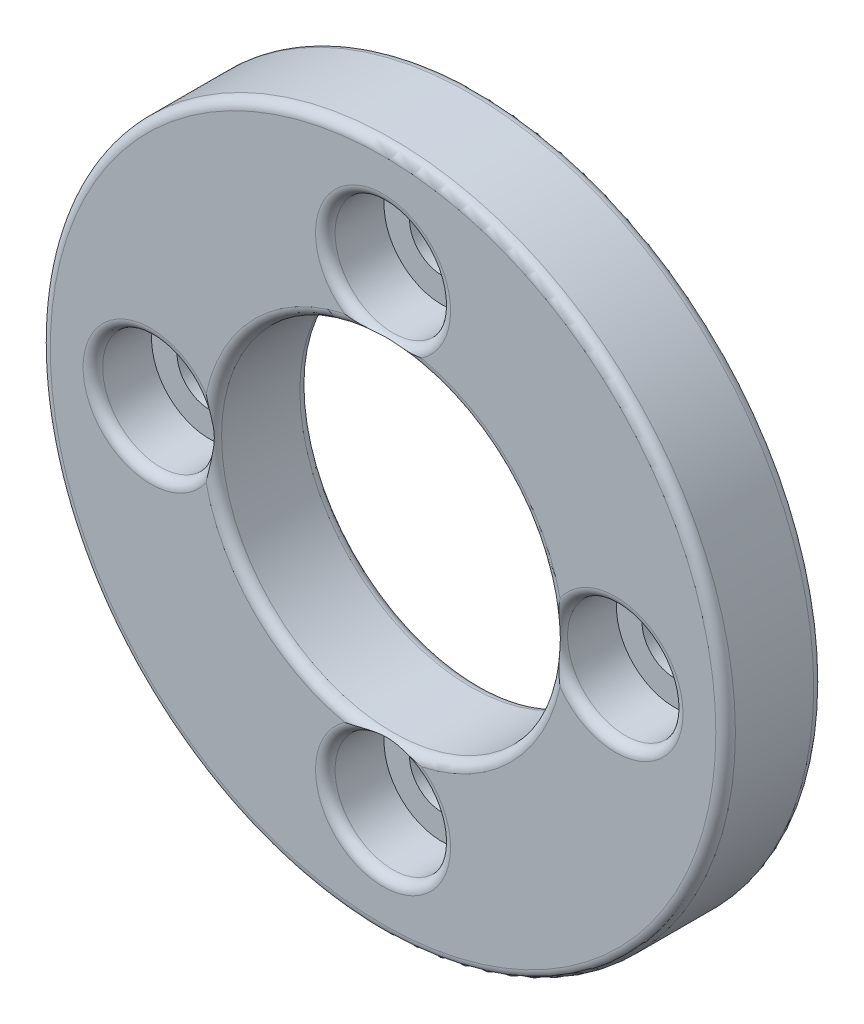
SolidWorks part; units mm, degrees
ref_plane "Ebene vorne" through (0, 0, 0) normal (0, 0, 1) x (1, 0, 0)
ref_plane "Ebene oben" through (0, 0, 0) normal (0, 1, 0) x (1, 0, 0)
ref_plane "Ebene rechts" through (0, 0, 0) normal (1, 0, 0) x (0, 0, -1)
sketch "Skizze1" plane through (0, 0, 0) normal (0, 0, 1) x (1, 0, 0)
  line L0 (0, 8.75) -> (0, 10.225) construction
  line L1 (0, 13.525) -> (0, 15) construction
  circle A0 centre (0, 0) radius 15
  circle A1 centre (0, 0) radius 8.75
  circle A2 centre (0, 0) radius 17.5
  circle A3 centre (0, 11.875) radius 1.65
  circle A4 centre (11.875, 0) radius 1.65
  circle A5 centre (0, -11.875) radius 1.65
  circle A6 centre (-11.875, 0) radius 1.65
  point P18 (0, 0)
  dimension "D1" = 30
  dimension "D2" = 17.5
  dimension "D3" = 35
  dimension "D4" = 3.3
  dimension "D5" = 4
extrude "Aufsatz-Linear austragen1" add sketch "Skizze1" along normal blind 5 contours A0 A6 A5 A4 A3 A1 | A2 A0 region at (-14.5757, 0, 0) region at (-17.005, 0, 0)
sketch "Skizze2" plane through (0, 0, 5) normal (0, 0, 1) x (1, 0, 0)
  circle A0 centre (0, 11.875) radius 2.95
  circle A1 centre (11.875, 0) radius 2.95
  circle A2 centre (0, -11.875) radius 2.95
  circle A3 centre (-11.875, 0) radius 2.95
  point P12 (0, 0)
  dimension "D1" = 5.9
  dimension "D2" = 4
extrude "Schnitt-Linear austragen1" cut sketch "Skizze2" against normal blind 3
fillet "Verrundung1" radius 0.5 12 edges at (17.5, 0, 0) (8.75, 0, 0) (1.65, 11.875, 0) (13.525, 0, 0) (1.65, -11.875, 0) (-10.225, 0, 0) (17.5, 0, 5) (8.75, 0, 5) (-8.925, 0, 5) (2.95, -11.875, 5) (14.825, 0, 5) (2.95, 11.875, 5)
